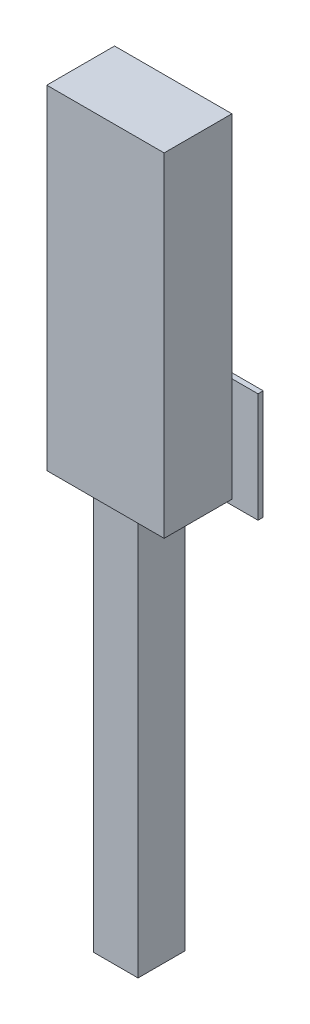
SolidWorks part; units mm, degrees
ref_plane "Front Plane" through (0, 0, 0) normal (0, 0, 1) x (1, 0, 0)
ref_plane "Top Plane" through (0, 0, 0) normal (0, 1, 0) x (1, 0, 0)
ref_plane "Right Plane" through (0, 0, 0) normal (1, 0, 0) x (0, 0, -1)
other "Configuration Table"
sketch "Sketch1" plane through (0, 0, 0) normal (1, 0, 0) x (0, 0, -1)
  line L1 (-51, 155) -> (-77, 155)
  line L2 (-51, 155) -> (-51, 283)
  line L3 (-51, 283) -> (-77, 283)
  line L4 (-77, 155) -> (-77, 283)
  line L5 (-51, 155) -> (-77, 283) construction
  line L6 (-51, 283) -> (-77, 155) construction
  point P0 (-64, 219)
extrude "reflector" add sketch "Sketch1" along normal blind 45 from offset 44 separate body
sketch "Sketch2" plane through (0, 0, 0) normal (1, 0, 0) x (0, 0, -1)
  line L1 (-45, 158) -> (-74, 158)
  line L2 (-45, 158) -> (-45, 280)
  line L3 (-45, 280) -> (-74, 280)
  line L4 (-74, 158) -> (-74, 280)
  line L5 (-45, 158) -> (-74, 280) construction
  line L6 (-45, 280) -> (-74, 158) construction
  point P0 (-59.5, 219)
extrude "cavity" add sketch "Sketch2" along normal blind 39 from offset 47 separate body
combine bodies "Combine1" operation type subtract main body 102 bodies to subtract 103
sketch "Sketch3" plane through (0, 0, 0) normal (0, 1, 0) x (1, 0, 0)
  circle A0 centre (66.34, -59.5) radius 5
extrude "r7s_lamp" add sketch "Sketch3" along normal blind 118 from offset 160 separate body
sketch "Sketch4" plane through (0, 0, 0) normal (1, 0, 0) x (0, 0, -1)
  line L0 (-77, 155) -> (-51, 155) construction
  line L1 (-55, 0) -> (-73, 0)
  line L2 (-55, 0) -> (-55, 155)
  line L3 (-55, 155) -> (-73, 155)
  line L4 (-73, 0) -> (-73, 155)
  line L5 (-55, 0) -> (-73, 155) construction
  line L6 (-55, 155) -> (-73, 0) construction
  point P0 (-64, 77.5)
extrude "heater_column" add sketch "Sketch4" along normal blind 17 from offset 58 separate body
sketch "Sketch5" plane through (0, 0, 0) normal (1, 0, 0) x (0, 0, -1)
  line L1 (-46, 150) -> (-48, 150)
  line L2 (-46, 150) -> (-46, 192)
  line L3 (-46, 192) -> (-48, 192)
  line L4 (-48, 150) -> (-48, 192)
  line L5 (-46, 150) -> (-48, 192) construction
  line L6 (-46, 192) -> (-48, 150) construction
  point P0 (-47, 171)
extrude "heat_shield" add sketch "Sketch5" along normal blind 66 from offset 30 separate body
